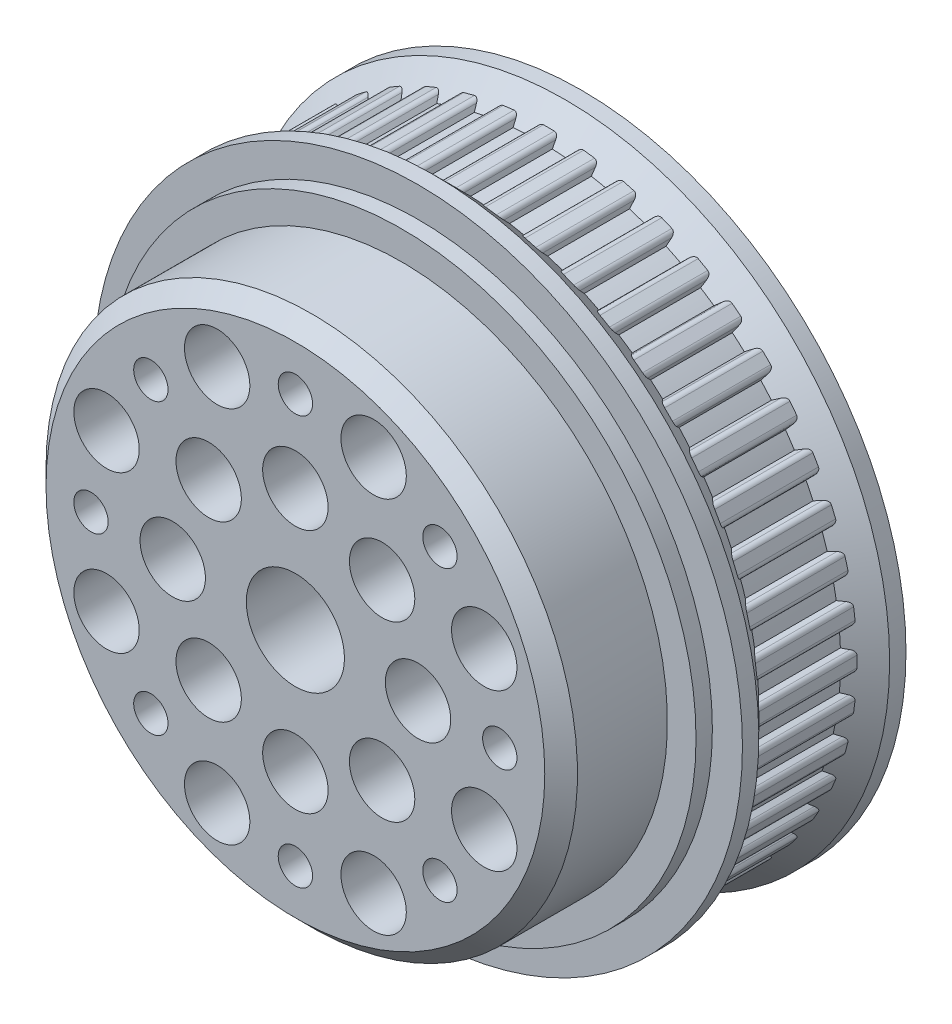
SolidWorks part; units mm, degrees
material "ABS"
ref_plane "Plan de face" through (0, 0, 0) normal (0, 0, 1) x (1, 0, 0)
ref_plane "Plan de dessus" through (0, 0, 0) normal (0, 1, 0) x (1, 0, 0)
ref_plane "Plan de droite" through (0, 0, 0) normal (1, 0, 0) x (0, 0, -1)
sketch "Esquisse1" plane through (0, 0, 0) normal (0, 0, 1) x (1, 0, 0)
  line L0 (0, 0) -> (0, 38.195) construction
  line L1 (0, 0) -> (4.9854, 37.8682) construction
  line L2 (1.4855, 36.4258) -> (3.2817, 36.3081)
  line L3 (0, 0) -> (2.3836, 36.367) construction
  line L4 (0, 37.6783) -> (0.6704, 37.6783)
  line L5 (1.2464, 37.2462) -> (1.4855, 36.4258)
  line L6 (4.918, 37.356) -> (4.2534, 37.4435)
  line L7 (3.6259, 37.0903) -> (3.2817, 36.3081)
  line L8 (6.2274, 35.9203) -> (7.9928, 35.5691)
  line L9 (4.918, 37.356) -> (5.5827, 37.2685)
  line L10 (6.0974, 36.7649) -> (6.2274, 35.9203)
  line L11 (9.7519, 36.3945) -> (9.1043, 36.568)
  line L12 (8.4361, 36.2997) -> (7.9928, 35.5691)
  line L13 (10.8626, 34.8002) -> (12.5671, 34.2216)
  line L14 (9.7519, 36.3945) -> (10.3994, 36.221)
  line L15 (10.844, 35.6545) -> (10.8626, 34.8002)
  line L16 (14.4189, 34.8103) -> (13.7995, 35.0668)
  line L17 (13.102, 34.888) -> (12.5671, 34.2216)
  line L18 (15.312, 33.0846) -> (16.9264, 32.2885)
  line L19 (14.4189, 34.8103) -> (15.0382, 34.5537)
  line L20 (15.4051, 33.9341) -> (15.312, 33.0846)
  line L21 (18.8392, 32.6304) -> (18.2586, 32.9656)
  line L22 (17.5437, 32.8794) -> (16.9264, 32.2885)
  line L23 (19.4994, 30.8029) -> (20.9961, 29.8029)
  line L24 (18.8392, 32.6304) -> (19.4197, 32.2952)
  line L25 (19.7025, 31.633) -> (19.4994, 30.8029)
  line L26 (22.9371, 29.8922) -> (22.4053, 30.3003)
  line L27 (21.6852, 30.3082) -> (20.9961, 29.8029)
  line L28 (23.3532, 27.9942) -> (24.7065, 26.8074)
  line L29 (22.9371, 29.8922) -> (23.469, 29.4841)
  line L30 (23.6629, 28.7907) -> (23.3532, 27.9942)
  line L31 (26.6426, 26.6426) -> (26.1686, 27.1166)
  line L32 (25.4557, 27.2184) -> (24.7065, 26.8074)
  line L33 (26.8074, 24.7065) -> (27.9942, 23.3532)
  line L34 (26.6426, 26.6426) -> (27.1166, 26.1686)
  line L35 (27.2184, 25.4557) -> (26.8074, 24.7065)
  line L36 (29.8922, 22.9371) -> (29.4841, 23.469)
  line L37 (28.7907, 23.6629) -> (27.9942, 23.3532)
  line L38 (29.8029, 20.9961) -> (30.8029, 19.4994)
  line L39 (29.8922, 22.9371) -> (30.3003, 22.4053)
  line L40 (30.3082, 21.6852) -> (29.8029, 20.9961)
  line L41 (32.6304, 18.8392) -> (32.2952, 19.4197)
  line L42 (31.633, 19.7025) -> (30.8029, 19.4994)
  line L43 (32.2885, 16.9264) -> (33.0846, 15.312)
  line L44 (32.6304, 18.8392) -> (32.9656, 18.2586)
  line L45 (32.8794, 17.5437) -> (32.2885, 16.9264)
  line L46 (34.8103, 14.4189) -> (34.5537, 15.0382)
  line L47 (33.9341, 15.4051) -> (33.0846, 15.312)
  line L48 (34.2216, 12.5671) -> (34.8002, 10.8626)
  line L49 (34.8103, 14.4189) -> (35.0668, 13.7995)
  line L50 (34.888, 13.102) -> (34.2216, 12.5671)
  line L51 (36.3945, 9.7519) -> (36.221, 10.3994)
  line L52 (35.6545, 10.844) -> (34.8002, 10.8626)
  line L53 (35.5691, 7.9928) -> (35.9203, 6.2274)
  line L54 (36.3945, 9.7519) -> (36.568, 9.1043)
  line L55 (36.2997, 8.4361) -> (35.5691, 7.9928)
  line L56 (37.356, 4.918) -> (37.2685, 5.5827)
  line L57 (36.7649, 6.0974) -> (35.9203, 6.2274)
  line L58 (36.3081, 3.2817) -> (36.4258, 1.4855)
  line L59 (37.356, 4.918) -> (37.4435, 4.2534)
  line L60 (37.0903, 3.6259) -> (36.3081, 3.2817)
  line L61 (37.6783, 0) -> (37.6783, 0.6704)
  line L62 (37.2462, 1.2464) -> (36.4258, 1.4855)
  line L63 (36.4258, -1.4855) -> (36.3081, -3.2817)
  line L64 (37.6783, 0) -> (37.6783, -0.6704)
  line L65 (37.2462, -1.2464) -> (36.4258, -1.4855)
  line L66 (37.356, -4.918) -> (37.4435, -4.2534)
  line L67 (37.0903, -3.6259) -> (36.3081, -3.2817)
  line L68 (35.9203, -6.2274) -> (35.5691, -7.9928)
  line L69 (37.356, -4.918) -> (37.2685, -5.5827)
  line L70 (36.7649, -6.0974) -> (35.9203, -6.2274)
  line L71 (36.3945, -9.7519) -> (36.568, -9.1043)
  line L72 (36.2997, -8.4361) -> (35.5691, -7.9928)
  line L73 (34.8002, -10.8626) -> (34.2216, -12.5671)
  line L74 (36.3945, -9.7519) -> (36.221, -10.3994)
  line L75 (35.6545, -10.844) -> (34.8002, -10.8626)
  line L76 (34.8103, -14.4189) -> (35.0668, -13.7995)
  line L77 (34.888, -13.102) -> (34.2216, -12.5671)
  line L78 (33.0846, -15.312) -> (32.2885, -16.9264)
  line L79 (34.8103, -14.4189) -> (34.5537, -15.0382)
  line L80 (33.9341, -15.4051) -> (33.0846, -15.312)
  line L81 (32.6304, -18.8392) -> (32.9656, -18.2586)
  line L82 (32.8794, -17.5437) -> (32.2885, -16.9264)
  line L83 (30.8029, -19.4994) -> (29.8029, -20.9961)
  line L84 (32.6304, -18.8392) -> (32.2952, -19.4197)
  line L85 (31.633, -19.7025) -> (30.8029, -19.4994)
  line L86 (29.8922, -22.9371) -> (30.3003, -22.4053)
  line L87 (30.3082, -21.6852) -> (29.8029, -20.9961)
  line L88 (27.9942, -23.3532) -> (26.8074, -24.7065)
  line L89 (29.8922, -22.9371) -> (29.4841, -23.469)
  line L90 (28.7907, -23.6629) -> (27.9942, -23.3532)
  line L91 (26.6426, -26.6426) -> (27.1166, -26.1686)
  line L92 (27.2184, -25.4557) -> (26.8074, -24.7065)
  line L93 (24.7065, -26.8074) -> (23.3532, -27.9942)
  line L94 (26.6426, -26.6426) -> (26.1686, -27.1166)
  line L95 (25.4557, -27.2184) -> (24.7065, -26.8074)
  line L96 (22.9371, -29.8922) -> (23.469, -29.4841)
  line L97 (23.6629, -28.7907) -> (23.3532, -27.9942)
  line L98 (20.9961, -29.8029) -> (19.4994, -30.8029)
  line L99 (22.9371, -29.8922) -> (22.4053, -30.3003)
  line L100 (21.6852, -30.3082) -> (20.9961, -29.8029)
  line L101 (18.8392, -32.6304) -> (19.4197, -32.2952)
  line L102 (19.7025, -31.633) -> (19.4994, -30.8029)
  line L103 (16.9264, -32.2885) -> (15.312, -33.0846)
  line L104 (18.8392, -32.6304) -> (18.2586, -32.9656)
  line L105 (17.5437, -32.8794) -> (16.9264, -32.2885)
  line L106 (14.4189, -34.8103) -> (15.0382, -34.5537)
  line L107 (15.4051, -33.9341) -> (15.312, -33.0846)
  line L108 (12.5671, -34.2216) -> (10.8626, -34.8002)
  line L109 (14.4189, -34.8103) -> (13.7995, -35.0668)
  line L110 (13.102, -34.888) -> (12.5671, -34.2216)
  line L111 (9.7519, -36.3945) -> (10.3994, -36.221)
  line L112 (10.844, -35.6545) -> (10.8626, -34.8002)
  line L113 (7.9928, -35.5691) -> (6.2274, -35.9203)
  line L114 (9.7519, -36.3945) -> (9.1043, -36.568)
  line L115 (8.4361, -36.2997) -> (7.9928, -35.5691)
  line L116 (4.918, -37.356) -> (5.5827, -37.2685)
  line L117 (6.0974, -36.7649) -> (6.2274, -35.9203)
  line L118 (3.2817, -36.3081) -> (1.4855, -36.4258)
  line L119 (4.918, -37.356) -> (4.2534, -37.4435)
  line L120 (3.6259, -37.0903) -> (3.2817, -36.3081)
  line L121 (0, -37.6783) -> (0.6704, -37.6783)
  line L122 (1.2464, -37.2462) -> (1.4855, -36.4258)
  line L123 (-1.4855, -36.4258) -> (-3.2817, -36.3081)
  line L124 (0, -37.6783) -> (-0.6704, -37.6783)
  line L125 (-1.2464, -37.2462) -> (-1.4855, -36.4258)
  line L126 (-4.918, -37.356) -> (-4.2534, -37.4435)
  line L127 (-3.6259, -37.0903) -> (-3.2817, -36.3081)
  line L128 (-6.2274, -35.9203) -> (-7.9928, -35.5691)
  line L129 (-4.918, -37.356) -> (-5.5827, -37.2685)
  line L130 (-6.0974, -36.7649) -> (-6.2274, -35.9203)
  line L131 (-9.7519, -36.3945) -> (-9.1043, -36.568)
  line L132 (-8.4361, -36.2997) -> (-7.9928, -35.5691)
  line L133 (-10.8626, -34.8002) -> (-12.5671, -34.2216)
  line L134 (-9.7519, -36.3945) -> (-10.3994, -36.221)
  line L135 (-10.844, -35.6545) -> (-10.8626, -34.8002)
  line L136 (-14.4189, -34.8103) -> (-13.7995, -35.0668)
  line L137 (-13.102, -34.888) -> (-12.5671, -34.2216)
  line L138 (-15.312, -33.0846) -> (-16.9264, -32.2885)
  line L139 (-14.4189, -34.8103) -> (-15.0382, -34.5537)
  line L140 (-15.4051, -33.9341) -> (-15.312, -33.0846)
  line L141 (-18.8392, -32.6304) -> (-18.2586, -32.9656)
  line L142 (-17.5437, -32.8794) -> (-16.9264, -32.2885)
  line L143 (-19.4994, -30.8029) -> (-20.9961, -29.8029)
  line L144 (-18.8392, -32.6304) -> (-19.4197, -32.2952)
  line L145 (-19.7025, -31.633) -> (-19.4994, -30.8029)
  line L146 (-22.9371, -29.8922) -> (-22.4053, -30.3003)
  line L147 (-21.6852, -30.3082) -> (-20.9961, -29.8029)
  line L148 (-23.3532, -27.9942) -> (-24.7065, -26.8074)
  line L149 (-22.9371, -29.8922) -> (-23.469, -29.4841)
  line L150 (-23.6629, -28.7907) -> (-23.3532, -27.9942)
  line L151 (-26.6426, -26.6426) -> (-26.1686, -27.1166)
  line L152 (-25.4557, -27.2184) -> (-24.7065, -26.8074)
  line L153 (-26.8074, -24.7065) -> (-27.9942, -23.3532)
  line L154 (-26.6426, -26.6426) -> (-27.1166, -26.1686)
  line L155 (-27.2184, -25.4557) -> (-26.8074, -24.7065)
  line L156 (-29.8922, -22.9371) -> (-29.4841, -23.469)
  line L157 (-28.7907, -23.6629) -> (-27.9942, -23.3532)
  line L158 (-29.8029, -20.9961) -> (-30.8029, -19.4994)
  line L159 (-29.8922, -22.9371) -> (-30.3003, -22.4053)
  line L160 (-30.3082, -21.6852) -> (-29.8029, -20.9961)
  line L161 (-32.6304, -18.8392) -> (-32.2952, -19.4197)
  line L162 (-31.633, -19.7025) -> (-30.8029, -19.4994)
  line L163 (-32.2885, -16.9264) -> (-33.0846, -15.312)
  line L164 (-32.6304, -18.8392) -> (-32.9656, -18.2586)
  line L165 (-32.8794, -17.5437) -> (-32.2885, -16.9264)
  line L166 (-34.8103, -14.4189) -> (-34.5537, -15.0382)
  line L167 (-33.9341, -15.4051) -> (-33.0846, -15.312)
  line L168 (-34.2216, -12.5671) -> (-34.8002, -10.8626)
  line L169 (-34.8103, -14.4189) -> (-35.0668, -13.7995)
  line L170 (-34.888, -13.102) -> (-34.2216, -12.5671)
  line L171 (-36.3945, -9.7519) -> (-36.221, -10.3994)
  line L172 (-35.6545, -10.844) -> (-34.8002, -10.8626)
  line L173 (-35.5691, -7.9928) -> (-35.9203, -6.2274)
  line L174 (-36.3945, -9.7519) -> (-36.568, -9.1043)
  line L175 (-36.2997, -8.4361) -> (-35.5691, -7.9928)
  line L176 (-37.356, -4.918) -> (-37.2685, -5.5827)
  line L177 (-36.7649, -6.0974) -> (-35.9203, -6.2274)
  line L178 (-36.3081, -3.2817) -> (-36.4258, -1.4855)
  line L179 (-37.356, -4.918) -> (-37.4435, -4.2534)
  line L180 (-37.0903, -3.6259) -> (-36.3081, -3.2817)
  line L181 (-37.6783, 0) -> (-37.6783, -0.6704)
  line L182 (-37.2462, -1.2464) -> (-36.4258, -1.4855)
  line L183 (-36.4258, 1.4855) -> (-36.3081, 3.2817)
  line L184 (-37.6783, 0) -> (-37.6783, 0.6704)
  line L185 (-37.2462, 1.2464) -> (-36.4258, 1.4855)
  line L186 (-37.356, 4.918) -> (-37.4435, 4.2534)
  line L187 (-37.0903, 3.6259) -> (-36.3081, 3.2817)
  line L188 (-35.9203, 6.2274) -> (-35.5691, 7.9928)
  line L189 (-37.356, 4.918) -> (-37.2685, 5.5827)
  line L190 (-36.7649, 6.0974) -> (-35.9203, 6.2274)
  line L191 (-36.3945, 9.7519) -> (-36.568, 9.1043)
  line L192 (-36.2997, 8.4361) -> (-35.5691, 7.9928)
  line L193 (-34.8002, 10.8626) -> (-34.2216, 12.5671)
  line L194 (-36.3945, 9.7519) -> (-36.221, 10.3994)
  line L195 (-35.6545, 10.844) -> (-34.8002, 10.8626)
  line L196 (-34.8103, 14.4189) -> (-35.0668, 13.7995)
  line L197 (-34.888, 13.102) -> (-34.2216, 12.5671)
  line L198 (-33.0846, 15.312) -> (-32.2885, 16.9264)
  line L199 (-34.8103, 14.4189) -> (-34.5537, 15.0382)
  line L200 (-33.9341, 15.4051) -> (-33.0846, 15.312)
  line L201 (-32.6304, 18.8392) -> (-32.9656, 18.2586)
  line L202 (-32.8794, 17.5437) -> (-32.2885, 16.9264)
  line L203 (-30.8029, 19.4994) -> (-29.8029, 20.9961)
  line L204 (-32.6304, 18.8392) -> (-32.2952, 19.4197)
  line L205 (-31.633, 19.7025) -> (-30.8029, 19.4994)
  line L206 (-29.8922, 22.9371) -> (-30.3003, 22.4053)
  line L207 (-30.3082, 21.6852) -> (-29.8029, 20.9961)
  line L208 (-27.9942, 23.3532) -> (-26.8074, 24.7065)
  line L209 (-29.8922, 22.9371) -> (-29.4841, 23.469)
  line L210 (-28.7907, 23.6629) -> (-27.9942, 23.3532)
  line L211 (-26.6426, 26.6426) -> (-27.1166, 26.1686)
  line L212 (-27.2184, 25.4557) -> (-26.8074, 24.7065)
  line L213 (-24.7065, 26.8074) -> (-23.3532, 27.9942)
  line L214 (-26.6426, 26.6426) -> (-26.1686, 27.1166)
  line L215 (-25.4557, 27.2184) -> (-24.7065, 26.8074)
  line L216 (-22.9371, 29.8922) -> (-23.469, 29.4841)
  line L217 (-23.6629, 28.7907) -> (-23.3532, 27.9942)
  line L218 (-20.9961, 29.8029) -> (-19.4994, 30.8029)
  line L219 (-22.9371, 29.8922) -> (-22.4053, 30.3003)
  line L220 (-21.6852, 30.3082) -> (-20.9961, 29.8029)
  line L221 (-18.8392, 32.6304) -> (-19.4197, 32.2952)
  line L222 (-19.7025, 31.633) -> (-19.4994, 30.8029)
  line L223 (-16.9264, 32.2885) -> (-15.312, 33.0846)
  line L224 (-18.8392, 32.6304) -> (-18.2586, 32.9656)
  line L225 (-17.5437, 32.8794) -> (-16.9264, 32.2885)
  line L226 (-14.4189, 34.8103) -> (-15.0382, 34.5537)
  line L227 (-15.4051, 33.9341) -> (-15.312, 33.0846)
  line L228 (-12.5671, 34.2216) -> (-10.8626, 34.8002)
  line L229 (-14.4189, 34.8103) -> (-13.7995, 35.0668)
  line L230 (-13.102, 34.888) -> (-12.5671, 34.2216)
  line L231 (-9.7519, 36.3945) -> (-10.3994, 36.221)
  line L232 (-10.844, 35.6545) -> (-10.8626, 34.8002)
  line L233 (-7.9928, 35.5691) -> (-6.2274, 35.9203)
  line L234 (-9.7519, 36.3945) -> (-9.1043, 36.568)
  line L235 (-8.4361, 36.2997) -> (-7.9928, 35.5691)
  line L236 (-4.918, 37.356) -> (-5.5827, 37.2685)
  line L237 (-6.0974, 36.7649) -> (-6.2274, 35.9203)
  line L238 (-3.2817, 36.3081) -> (-1.4855, 36.4258)
  line L239 (-4.918, 37.356) -> (-4.2534, 37.4435)
  line L240 (-3.6259, 37.0903) -> (-3.2817, 36.3081)
  line L241 (0, 37.6783) -> (-0.6704, 37.6783)
  line L242 (-1.2464, 37.2462) -> (-1.4855, 36.4258)
  circle A0 centre (0, 0) radius 38.195 construction
  circle A1 centre (0, 0) radius 37.695 construction
  circle A2 centre (0, 0) radius 36.445 construction
  arc A3 (4.2534, 37.4435) -> (3.6259, 37.0903) centre (4.175, 36.8486) ccw
  arc A4 (1.2464, 37.2462) -> (0.6704, 37.6783) centre (0.6704, 37.0783) ccw
  arc A5 (9.1043, 36.568) -> (8.4361, 36.2997) centre (8.949, 35.9884) ccw
  arc A6 (6.0974, 36.7649) -> (5.5827, 37.2685) centre (5.5043, 36.6736) ccw
  arc A7 (13.7995, 35.0668) -> (13.102, 34.888) centre (13.5699, 34.5125) ccw
  arc A8 (10.844, 35.6545) -> (10.3994, 36.221) centre (10.2441, 35.6414) ccw
  arc A9 (18.2586, 32.9656) -> (17.5437, 32.8794) centre (17.9586, 32.446) ccw
  arc A10 (15.4051, 33.9341) -> (15.0382, 34.5537) centre (14.8086, 33.9994) ccw
  arc A11 (22.4053, 30.3003) -> (21.6852, 30.3082) centre (22.04, 29.8243) ccw
  arc A12 (19.7025, 31.633) -> (19.4197, 32.2952) centre (19.1197, 31.7756) ccw
  arc A13 (26.1686, 27.1166) -> (25.4557, 27.2184) centre (25.7443, 26.6924) ccw
  arc A14 (23.6629, 28.7907) -> (23.469, 29.4841) centre (23.1037, 29.0081) ccw
  arc A15 (29.4841, 23.469) -> (28.7907, 23.6629) centre (29.0081, 23.1037) ccw
  arc A16 (27.2184, 25.4557) -> (27.1166, 26.1686) centre (26.6924, 25.7443) ccw
  arc A17 (32.2952, 19.4197) -> (31.633, 19.7025) centre (31.7756, 19.1197) ccw
  arc A18 (30.3082, 21.6852) -> (30.3003, 22.4053) centre (29.8243, 22.04) ccw
  arc A19 (34.5537, 15.0382) -> (33.9341, 15.4051) centre (33.9994, 14.8086) ccw
  arc A20 (32.8794, 17.5437) -> (32.9656, 18.2586) centre (32.446, 17.9586) ccw
  arc A21 (36.221, 10.3994) -> (35.6545, 10.844) centre (35.6414, 10.2441) ccw
  arc A22 (34.888, 13.102) -> (35.0668, 13.7995) centre (34.5125, 13.5699) ccw
  arc A23 (37.2685, 5.5827) -> (36.7649, 6.0974) centre (36.6736, 5.5043) ccw
  arc A24 (36.2997, 8.4361) -> (36.568, 9.1043) centre (35.9884, 8.949) ccw
  arc A25 (37.6783, 0.6704) -> (37.2462, 1.2464) centre (37.0783, 0.6704) ccw
  arc A26 (37.0903, 3.6259) -> (37.4435, 4.2534) centre (36.8486, 4.175) ccw
  arc A27 (37.4435, -4.2534) -> (37.0903, -3.6259) centre (36.8486, -4.175) ccw
  arc A28 (37.2462, -1.2464) -> (37.6783, -0.6704) centre (37.0783, -0.6704) ccw
  arc A29 (36.568, -9.1043) -> (36.2997, -8.4361) centre (35.9884, -8.949) ccw
  arc A30 (36.7649, -6.0974) -> (37.2685, -5.5827) centre (36.6736, -5.5043) ccw
  arc A31 (35.0668, -13.7995) -> (34.888, -13.102) centre (34.5125, -13.5699) ccw
  arc A32 (35.6545, -10.844) -> (36.221, -10.3994) centre (35.6414, -10.2441) ccw
  arc A33 (32.9656, -18.2586) -> (32.8794, -17.5437) centre (32.446, -17.9586) ccw
  arc A34 (33.9341, -15.4051) -> (34.5537, -15.0382) centre (33.9994, -14.8086) ccw
  arc A35 (30.3003, -22.4053) -> (30.3082, -21.6852) centre (29.8243, -22.04) ccw
  arc A36 (31.633, -19.7025) -> (32.2952, -19.4197) centre (31.7756, -19.1197) ccw
  arc A37 (27.1166, -26.1686) -> (27.2184, -25.4557) centre (26.6924, -25.7443) ccw
  arc A38 (28.7907, -23.6629) -> (29.4841, -23.469) centre (29.0081, -23.1037) ccw
  arc A39 (23.469, -29.4841) -> (23.6629, -28.7907) centre (23.1037, -29.0081) ccw
  arc A40 (25.4557, -27.2184) -> (26.1686, -27.1166) centre (25.7443, -26.6924) ccw
  arc A41 (19.4197, -32.2952) -> (19.7025, -31.633) centre (19.1197, -31.7756) ccw
  arc A42 (21.6852, -30.3082) -> (22.4053, -30.3003) centre (22.04, -29.8243) ccw
  arc A43 (15.0382, -34.5537) -> (15.4051, -33.9341) centre (14.8086, -33.9994) ccw
  arc A44 (17.5437, -32.8794) -> (18.2586, -32.9656) centre (17.9586, -32.446) ccw
  arc A45 (10.3994, -36.221) -> (10.844, -35.6545) centre (10.2441, -35.6414) ccw
  arc A46 (13.102, -34.888) -> (13.7995, -35.0668) centre (13.5699, -34.5125) ccw
  arc A47 (5.5827, -37.2685) -> (6.0974, -36.7649) centre (5.5043, -36.6736) ccw
  arc A48 (8.4361, -36.2997) -> (9.1043, -36.568) centre (8.949, -35.9884) ccw
  arc A49 (0.6704, -37.6783) -> (1.2464, -37.2462) centre (0.6704, -37.0783) ccw
  arc A50 (3.6259, -37.0903) -> (4.2534, -37.4435) centre (4.175, -36.8486) ccw
  arc A51 (-4.2534, -37.4435) -> (-3.6259, -37.0903) centre (-4.175, -36.8486) ccw
  arc A52 (-1.2464, -37.2462) -> (-0.6704, -37.6783) centre (-0.6704, -37.0783) ccw
  arc A53 (-9.1043, -36.568) -> (-8.4361, -36.2997) centre (-8.949, -35.9884) ccw
  arc A54 (-6.0974, -36.7649) -> (-5.5827, -37.2685) centre (-5.5043, -36.6736) ccw
  arc A55 (-13.7995, -35.0668) -> (-13.102, -34.888) centre (-13.5699, -34.5125) ccw
  arc A56 (-10.844, -35.6545) -> (-10.3994, -36.221) centre (-10.2441, -35.6414) ccw
  arc A57 (-18.2586, -32.9656) -> (-17.5437, -32.8794) centre (-17.9586, -32.446) ccw
  arc A58 (-15.4051, -33.9341) -> (-15.0382, -34.5537) centre (-14.8086, -33.9994) ccw
  arc A59 (-22.4053, -30.3003) -> (-21.6852, -30.3082) centre (-22.04, -29.8243) ccw
  arc A60 (-19.7025, -31.633) -> (-19.4197, -32.2952) centre (-19.1197, -31.7756) ccw
  arc A61 (-26.1686, -27.1166) -> (-25.4557, -27.2184) centre (-25.7443, -26.6924) ccw
  arc A62 (-23.6629, -28.7907) -> (-23.469, -29.4841) centre (-23.1037, -29.0081) ccw
  arc A63 (-29.4841, -23.469) -> (-28.7907, -23.6629) centre (-29.0081, -23.1037) ccw
  arc A64 (-27.2184, -25.4557) -> (-27.1166, -26.1686) centre (-26.6924, -25.7443) ccw
  arc A65 (-32.2952, -19.4197) -> (-31.633, -19.7025) centre (-31.7756, -19.1197) ccw
  arc A66 (-30.3082, -21.6852) -> (-30.3003, -22.4053) centre (-29.8243, -22.04) ccw
  arc A67 (-34.5537, -15.0382) -> (-33.9341, -15.4051) centre (-33.9994, -14.8086) ccw
  arc A68 (-32.8794, -17.5437) -> (-32.9656, -18.2586) centre (-32.446, -17.9586) ccw
  arc A69 (-36.221, -10.3994) -> (-35.6545, -10.844) centre (-35.6414, -10.2441) ccw
  arc A70 (-34.888, -13.102) -> (-35.0668, -13.7995) centre (-34.5125, -13.5699) ccw
  arc A71 (-37.2685, -5.5827) -> (-36.7649, -6.0974) centre (-36.6736, -5.5043) ccw
  arc A72 (-36.2997, -8.4361) -> (-36.568, -9.1043) centre (-35.9884, -8.949) ccw
  arc A73 (-37.6783, -0.6704) -> (-37.2462, -1.2464) centre (-37.0783, -0.6704) ccw
  arc A74 (-37.0903, -3.6259) -> (-37.4435, -4.2534) centre (-36.8486, -4.175) ccw
  arc A75 (-37.4435, 4.2534) -> (-37.0903, 3.6259) centre (-36.8486, 4.175) ccw
  arc A76 (-37.2462, 1.2464) -> (-37.6783, 0.6704) centre (-37.0783, 0.6704) ccw
  arc A77 (-36.568, 9.1043) -> (-36.2997, 8.4361) centre (-35.9884, 8.949) ccw
  arc A78 (-36.7649, 6.0974) -> (-37.2685, 5.5827) centre (-36.6736, 5.5043) ccw
  arc A79 (-35.0668, 13.7995) -> (-34.888, 13.102) centre (-34.5125, 13.5699) ccw
  arc A80 (-35.6545, 10.844) -> (-36.221, 10.3994) centre (-35.6414, 10.2441) ccw
  arc A81 (-32.9656, 18.2586) -> (-32.8794, 17.5437) centre (-32.446, 17.9586) ccw
  arc A82 (-33.9341, 15.4051) -> (-34.5537, 15.0382) centre (-33.9994, 14.8086) ccw
  arc A83 (-30.3003, 22.4053) -> (-30.3082, 21.6852) centre (-29.8243, 22.04) ccw
  arc A84 (-31.633, 19.7025) -> (-32.2952, 19.4197) centre (-31.7756, 19.1197) ccw
  arc A85 (-27.1166, 26.1686) -> (-27.2184, 25.4557) centre (-26.6924, 25.7443) ccw
  arc A86 (-28.7907, 23.6629) -> (-29.4841, 23.469) centre (-29.0081, 23.1037) ccw
  arc A87 (-23.469, 29.4841) -> (-23.6629, 28.7907) centre (-23.1037, 29.0081) ccw
  arc A88 (-25.4557, 27.2184) -> (-26.1686, 27.1166) centre (-25.7443, 26.6924) ccw
  arc A89 (-19.4197, 32.2952) -> (-19.7025, 31.633) centre (-19.1197, 31.7756) ccw
  arc A90 (-21.6852, 30.3082) -> (-22.4053, 30.3003) centre (-22.04, 29.8243) ccw
  arc A91 (-15.0382, 34.5537) -> (-15.4051, 33.9341) centre (-14.8086, 33.9994) ccw
  arc A92 (-17.5437, 32.8794) -> (-18.2586, 32.9656) centre (-17.9586, 32.446) ccw
  arc A93 (-10.3994, 36.221) -> (-10.844, 35.6545) centre (-10.2441, 35.6414) ccw
  arc A94 (-13.102, 34.888) -> (-13.7995, 35.0668) centre (-13.5699, 34.5125) ccw
  arc A95 (-5.5827, 37.2685) -> (-6.0974, 36.7649) centre (-5.5043, 36.6736) ccw
  arc A96 (-8.4361, 36.2997) -> (-9.1043, 36.568) centre (-8.949, 35.9884) ccw
  arc A97 (-0.6704, 37.6783) -> (-1.2464, 37.2462) centre (-0.6704, 37.0783) ccw
  arc A98 (-3.6259, 37.0903) -> (-4.2534, 37.4435) centre (-4.175, 36.8486) ccw
  circle A99 centre (0, 0) radius 30
  point P22 (3.8071, 37.5023)
  point P25 (1.1205, 37.6783)
  point P492 (0, 0)
  dimension "D1" = 76.39
  dimension "D3" = 0.5
  dimension "D4" = 1.25
  dimension "D9" = 0.6
  dimension "D11" = 60
  dimension "D2" = 7.5
  dimension "D5" = 3.75
  dimension "D6" = 20
  dimension "D7" = 20
  dimension "D8" = 1.8
  dimension "D10" = 48
extrude "Boss.-Extru.1" add sketch "Esquisse1" along normal blind 16
sketch "Esquisse2" plane through (0, 0, 0) normal (0, 1, 0) x (1, 0, 0)
  line L0 (0, 0) -> (0, -16) construction
  line L2 (0.6704, -16) -> (-0.6704, -16) construction
  line L4 (-6, 2) -> (-6, -18)
  line L5 (-6, -18) -> (-39.6783, -18)
  line L6 (-39.6783, -18) -> (-39.6783, -16)
  line L7 (-39.6783, -16) -> (-36.6783, -13)
  line L8 (-36.6783, -13) -> (-36.6783, -3)
  line L9 (-36.6783, -3) -> (-39.6783, 0)
  line L10 (-39.6783, 0) -> (-39.6783, 2)
  line L11 (-39.6783, 2) -> (-6, 2)
  line L12 (0, -8) -> (-6, -8) construction
  line L13 (-37.6783, -16) -> (-37.6783, 0) construction
  point P7 (-42.7073, -3.9717)
  point P14 (-38.8646, 2)
  dimension "D1" = 2
  dimension "D2" = 45
  dimension "D3" = 2
  dimension "D4" = 45
  dimension "D5" = 20
  dimension "D6" = 2
  dimension "D7" = 6
  dimension "D8" = 10
revolve "Révolution1" add sketch "Esquisse2" angle 360 about L0
sketch "Esquisse4" plane through (0, 0, 18) normal (0, 0, 1) x (1, 0, 0)
  circle A0 centre (0, 0) radius 36
  circle A2 centre (0, 0) radius 6
  dimension "D1" = 72
  dimension "D2" = 12
extrude "Boss.-Extru.2" add sketch "Esquisse4" along normal blind 2
sketch "Esquisse5" plane through (0, 0, 20) normal (0, 0, 1) x (1, 0, 0)
  circle A0 centre (0, 0) radius 6 construction
  circle A1 centre (0, 0) radius 6
  circle A2 centre (0, 0) radius 32.5
  dimension "D1" = 65
extrude "Boss.-Extru.3" add sketch "Esquisse5" along normal blind 13
sketch "Esquisse3" plane through (0, 0, -2) normal (0, 0, -1) x (-1, 0, 0)
  circle A0 centre (0, 0) radius 25 construction
  circle A1 centre (0, 25) radius 2.1
  circle A2 centre (17.6777, 17.6777) radius 2.1
  circle A3 centre (25, 0) radius 2.1
  circle A4 centre (17.6777, -17.6777) radius 2.1
  circle A5 centre (0, -25) radius 2.1
  circle A6 centre (-17.6777, -17.6777) radius 2.1
  circle A7 centre (-25, 0) radius 2.1
  circle A8 centre (-17.6777, 17.6777) radius 2.1
  point P5 (0, 0)
  point P6 (0, 0)
  point P21 (0, 0)
  point P22 (0, 0)
  dimension "D1" = 50
  dimension "D2" = 4.2
  dimension "D3" = 8
extrude "Enlèv. mat.-Extru.1" cut sketch "Esquisse3" against normal through all
sketch "Esquisse6" plane through (0, 0, 33) normal (0, 0, 1) x (1, 0, 0)
  line L0 (-25, 0) -> (0, 0) construction
  line L1 (0, 0) -> (-23.097, 9.5671) construction
  circle A0 centre (0, 0) radius 15 construction
  circle A1 centre (0, 15) radius 4
  circle A2 centre (10.6066, 10.6066) radius 4
  circle A3 centre (15, 0) radius 4
  circle A4 centre (10.6066, -10.6066) radius 4
  circle A5 centre (0, -15) radius 4
  circle A6 centre (-10.6066, -10.6066) radius 4
  circle A7 centre (-15, 0) radius 4
  circle A8 centre (-10.6066, 10.6066) radius 4
  circle A9 centre (0, 0) radius 25 construction
  circle A10 centre (-23.097, 9.5671) radius 4
  circle A11 centre (-9.5671, 23.097) radius 4
  circle A12 centre (9.5671, 23.097) radius 4
  circle A13 centre (23.097, 9.5671) radius 4
  circle A14 centre (23.097, -9.5671) radius 4
  circle A15 centre (9.5671, -23.097) radius 4
  circle A16 centre (-9.5671, -23.097) radius 4
  circle A17 centre (-23.097, -9.5671) radius 4
  point P20 (0, 0)
  point P40 (0, 0)
  dimension "D1" = 30
  dimension "D2" = 8
  dimension "D4" = 50
  dimension "D5" = 8
  dimension "D6" = 22.5
  dimension "D3" = 8
  dimension "D7" = 8
extrude "Enlèv. mat.-Extru.2" cut sketch "Esquisse6" against normal through all
chamfer "Chanfrein1" distance 2 angle 45 1 edges at (32.5, 0, 33)
